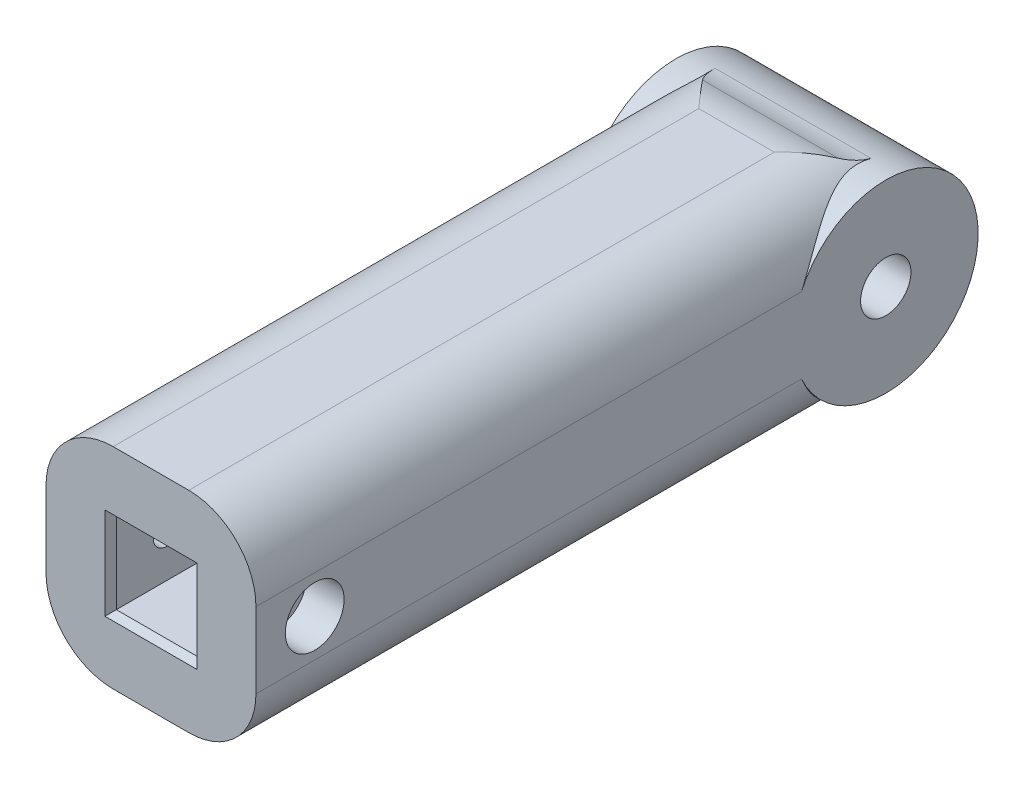
SolidWorks part; units mm, degrees
ref_plane "Спереди" through (0, 0, 0) normal (0, 0, 1) x (1, 0, 0)
ref_plane "Сверху" through (0, 0, 0) normal (0, 1, 0) x (1, 0, 0)
ref_plane "Справа" through (0, 0, 0) normal (1, 0, 0) x (0, 0, -1)
sketch "Sketch2" plane through (0, 0, 0) normal (0, 0, 1) x (1, 0, 0)
  line L1 (12.5, -12.5) -> (-12.5, -12.5)
  line L2 (12.5, -12.5) -> (12.5, 12.5)
  line L3 (12.5, 12.5) -> (-12.5, 12.5)
  line L4 (-12.5, -12.5) -> (-12.5, 12.5)
  line L5 (12.5, -12.5) -> (-12.5, 12.5) construction
  line L6 (12.5, 12.5) -> (-12.5, -12.5) construction
  line L7 (5.125, -5.125) -> (-5.125, -5.125)
  line L8 (5.125, -5.125) -> (5.125, 5.125)
  line L9 (5.125, 5.125) -> (-5.125, 5.125)
  line L10 (-5.125, -5.125) -> (-5.125, 5.125)
  line L11 (5.125, -5.125) -> (-5.125, 5.125) construction
  line L12 (5.125, 5.125) -> (-5.125, -5.125) construction
  point P0 (0, 0)
  point P6 (0, 0)
  dimension "D1" = 25
  dimension "D2" = 10.25
extrude "Boss-Extrude1" add sketch "Sketch2" along normal blind 85
fillet "Fillet1" radius 8 4 edges at (12.5, -12.5, 42.5) (12.5, 12.5, 42.5) (-12.5, -12.5, 42.5) (-12.5, 12.5, 42.5)
sketch "Sketch3" plane through (-12.5, 0, 0) normal (-1, 0, 0) x (0, 0, 1)
  line L0 (0, 0) -> (85, 0) construction
  line L1 (0, 4.5) -> (0, -4.5) construction
  line L2 (85, 4.5) -> (85, -4.5) construction
  circle A0 centre (10, 0) radius 3
  dimension "D1" = 6
  dimension "D2" = 10
extrude "Cut-Extrude1" cut sketch "Sketch3" against normal through all
sketch "Sketch4" plane through (5.125, 0, 0) normal (-1, 0, 0) x (0, 0, 1)
  circle A0 centre (10, 0) radius 11
  circle A1 centre (10, 0) radius 3
  circle A2 centre (10, 0) radius 3 construction
  dimension "D1" = 22
extrude "Boss-Extrude2" add sketch "Sketch4" against normal up to surface (7.375 mm away) up to face at (12.5, 0, 13)
sketch "Sketch5" plane through (-5.125, 0, 0) normal (1, 0, 0) x (0, 0, -1)
  circle A0 centre (-10, 0) radius 11
  circle A1 centre (-9.4923, 0) radius 3
  circle A2 centre (-10, 0) radius 3 construction
  dimension "D1" = 22
extrude "Boss-Extrude3" add sketch "Sketch5" against normal up to surface (7.375 mm away) up to face at (-12.5, 0, 13)
sketch "Sketch6" plane through (12.5, 0, 0) normal (1, 0, 0) x (0, 0, -1)
  line L0 (-10, -27.3297) -> (-10, 27.3297) construction
  line L1 (-13, 0) -> (-7, 0) construction
  line L2 (-10, 11) -> (-10, 16.9718)
  line L3 (-10, 16.9718) -> (7.792, 16.9718)
  line L4 (7.792, 16.9718) -> (7.792, -18.6645)
  line L5 (7.792, -18.6645) -> (-10, -18.6645)
  line L6 (-10, -18.6645) -> (-10, -11)
  circle A0 centre (-10, 0) radius 3 construction
  arc A1 (-20.0374, -4.5) -> (-20.0374, 4.5) centre (-10, 0) ccw construction
  arc A2 (-10, 11) -> (-10, -11) centre (-10, 0) cw
  point P4 (-10, 0)
  point P11 (-10, 0)
extrude "Cut-Extrude2" cut sketch "Sketch6" against normal through all
fillet "Fillet2" radius 10 2 edges at (0, -12.5, 10) (0, 12.5, 10)
fillet "Fillet3" radius 10 2 edges at (0, -11, 10) (0, 11, 10)
sketch "Sketch7" plane through (-12.5, 0, 0) normal (-1, 0, 0) x (0, 0, 1)
  line L0 (85, 0) -> (12.4923, 0) construction
  line L1 (85, 4.5) -> (85, -4.5) construction
  line L2 (85, 4.5) -> (20.0374, 4.5) construction
  line L3 (76.375, 2.8146) -> (74.75, 0)
  line L4 (74.75, 0) -> (76.375, -2.8146)
  line L5 (76.375, -2.8146) -> (79.625, -2.8146)
  line L6 (79.625, -2.8146) -> (81.25, 0)
  line L7 (81.25, 0) -> (79.625, 2.8146)
  line L8 (79.625, 2.8146) -> (76.375, 2.8146)
  arc A0 (9.7462, -2.9892) -> (9.7462, 2.9892) centre (9.4923, 0) ccw construction
  circle A1 centre (78, 0) radius 3.25 construction
  dimension "D1" = 6.5
  dimension "D2" = 7
extrude "Cut-Extrude3" cut sketch "Sketch7" against normal blind 4.5
sketch "Sketch8" plane through (-8, 0, 0) normal (-1, 0, 0) x (0, 0, 1)
  line L0 (78, 2.8146) -> (78, -2.8146) construction
  line L1 (79.625, 2.8146) -> (76.375, 2.8146) construction
  line L2 (76.375, -2.8146) -> (79.625, -2.8146) construction
  circle A0 centre (78, 0) radius 1.6
  dimension "D1" = 3.2
extrude "Cut-Extrude4" cut sketch "Sketch8" against normal through all
sketch "Sketch9" plane through (12.5, 0, 0) normal (1, 0, 0) x (0, 0, -1)
  circle A0 centre (-78, 0) radius 3.5
  dimension "D1" = 7
extrude "Cut-Extrude5" cut sketch "Sketch9" against normal blind 4.5
chamfer "Chamfer1" distance 1 angle 20 4 edges at (0, -5.125, 85) (5.125, 0, 85) (-5.125, 0, 85) (0, 5.125, 85)
